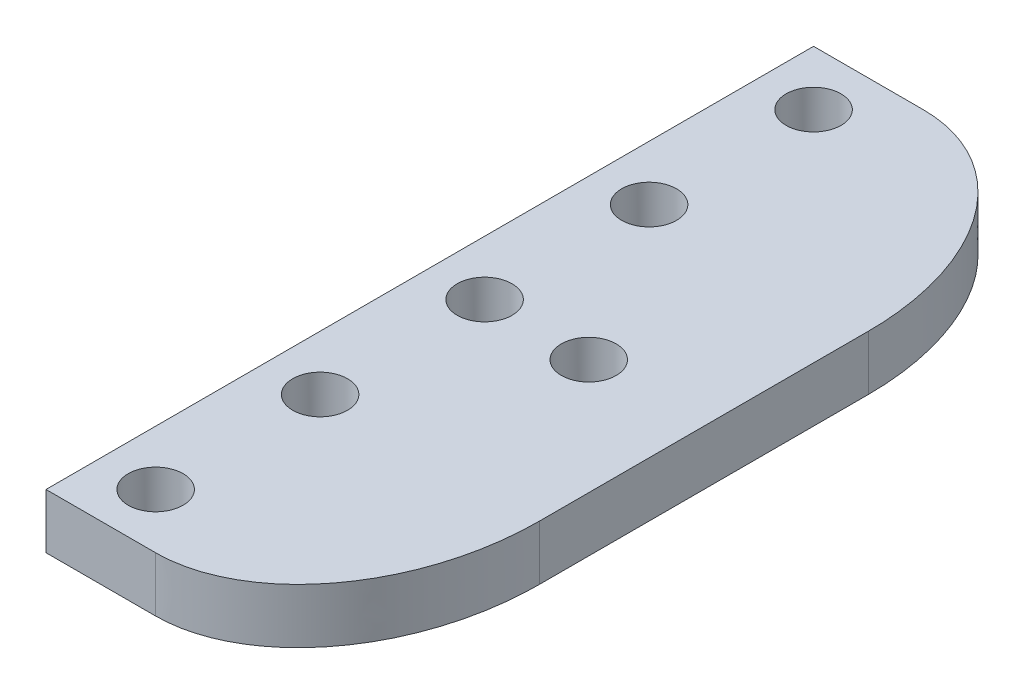
SolidWorks part; units mm, degrees
ref_plane "Front Plane" through (0, 0, 0) normal (0, 0, 1) x (1, 0, 0)
ref_plane "Top Plane" through (0, 0, 0) normal (0, 1, 0) x (1, 0, 0)
ref_plane "Right Plane" through (0, 0, 0) normal (1, 0, 0) x (0, 0, -1)
sketch "Sketch1" plane through (0, 0, 0) normal (0, 0, 1) x (1, 0, 0)
  line L0 (6.5, 2.5) -> (12.5, 2.5)
  line L1 (-12.5, -2.5) -> (12.5, -2.5)
  line L2 (-12.5, -2.5) -> (-12.5, 2.5)
  line L3 (-12.5, 2.5) -> (6.5, 2.5)
  line L4 (12.5, -2.5) -> (12.5, 2.5)
  line L5 (-12.5, -2.5) -> (12.5, 2.5) construction
  line L6 (-12.5, 2.5) -> (12.5, -2.5) construction
  point P0 (0, 0)
  point P6 (0, 0)
  point P7 (0, 0)
  point P8 (0, 0)
  point P10 (0, 0)
  dimension "D1" = 25
  dimension "D2" = 5
extrude "Boss-Extrude1" add sketch "Sketch1" along normal blind 70
sketch "Sketch2" plane through (0, 2.5, 0) normal (0, 1, 0) x (1, 0, 0)
  line L0 (12.5, 0) -> (-12.5, 0) construction
  line L5 (12.5, -70) -> (-12.5, -70) construction
  line L11 (-12.5, -70) -> (-12.5, 0) construction
  line L24 (12.5, -70) -> (12.5, 0) construction
  line L32 (12.5, -70) -> (-12.5, -70) construction
  line L33 (-10.5, -35) -> (-1.5, -35) construction
  line L34 (12.5, 0) -> (-12.5, 0) construction
  circle A0 centre (-7.5, -5) radius 2.5
  circle A2 centre (-7.5, -20) radius 2.5
  circle A3 centre (-7.5, -35) radius 2.5
  circle A4 centre (-7.5, -50) radius 2.5
  circle A5 centre (-7.5, -65) radius 2.5
  circle A6 centre (2, -35) radius 2.5
  dimension "D7" = 10.5
  dimension "D3" = 5
  dimension "D6" = 5
  dimension "D1" = 5
  dimension "D2" = 5
  dimension "D4" = 5
  dimension "D5" = 5
extrude "Cut-Extrude2" cut sketch "Sketch2" against normal through all both and the other way through all contours A0 | A2 | A6 L33 | L33 A6 | A4 | A5 | A3 region at (-7.5, 2.5, 5) region at (-7.5, 2.5, 20) region at (-7.5, 2.5, 50) region at (-7.5, 2.5, 65) region at (2, 2.5, 35)
fillet "Fillet1" radius 15 2 edges at (12.5, 0, 70) (12.5, 0, 0) second distance 20 first distance on face at (0, 0, 70) first distance on face at (0, 0, 0)
